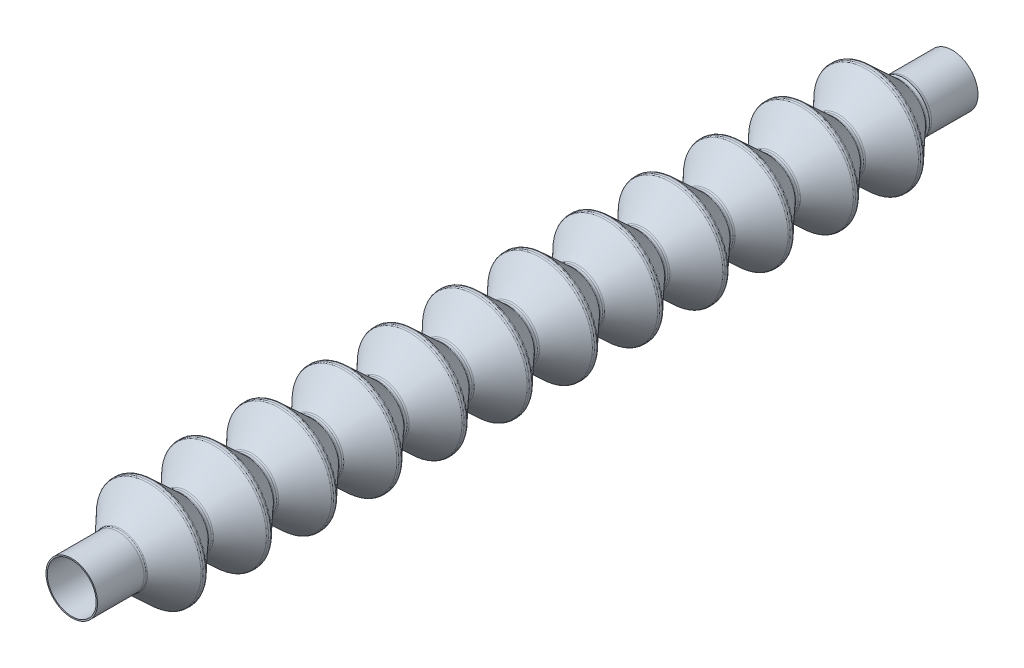
SolidWorks part; units mm, degrees
ref_plane "Front Plane" through (0, 0, 0) normal (0, 0, 1) x (1, 0, 0)
ref_plane "Top Plane" through (0, 0, 0) normal (0, 1, 0) x (1, 0, 0)
ref_plane "Right Plane" through (0, 0, 0) normal (1, 0, 0) x (0, 0, -1)
sketch "Sketch1" plane through (0, 0, 0) normal (1, 0, 0) x (0, 0, -1)
  line L0 (-152.4, 0) -> (152.4, 0) construction
  line L1 (0, -20.6375) -> (0, 20.6375) construction
  line L2 (-152.4, -9.525) -> (-152.4, 9.525) construction
  line L3 (-152.4, 0) -> (-171.45, 0) construction
  line L4 (152.4, 0) -> (171.45, 0) construction
  point P0 (-85.725, 0)
  point P3 (-152.4, 20.6375)
  point P4 (0, 0)
  point P8 (0, 0)
  point P11 (-152.4, 0)
  point P12 (0, 20.1295)
  point P13 (-152.4, 4.7625)
  point P14 (152.4, 20.6375)
  dimension "Retracted Length" = 66.675
  dimension "OD" = 41.275
  dimension "ID" = 19.05
  dimension "Required ID Clearance" = 4.7625
  dimension "Extended Length" = 304.8
  dimension "Cuff Length" = 19.05
sketch "Sketch2" plane through (0, 0, 0) normal (1, 0, 0) x (0, 0, -1)
  line L1 (-152.4, 9.525) -> (152.4, 9.525) construction
  line L7 (-152.4, 10.2195) -> (-141.224, 20.6375)
  line L9 (-152.4, 9.525) -> (-141.224, 19.943) construction
  line L108 (-153.8304, 10.8584) -> (-152.4, 9.525) construction
  line L109 (-152.4, 9.525) -> (-140.8776, 20.2659) construction
  line L163 (-152.4, 20.6375) -> (152.4, 20.6375) construction
  line L164 (-141.224, 20.6375) -> (-139.7, 20.6375)
  line L165 (-139.7, 20.6375) -> (-128.524, 10.2195)
  line L166 (-141.224, 19.943) -> (-139.7, 19.943) construction
  line L167 (-139.7, 19.943) -> (-128.524, 9.525) construction
  line L168 (-152.4, 9.525) -> (-141.224, 19.943)
  line L169 (-128.524, 10.2195) -> (-127, 10.2195)
  line L170 (-127, 10.2195) -> (-115.824, 20.6375)
  line L171 (-141.224, 19.943) -> (-139.7, 19.943)
  line L172 (-115.824, 20.6375) -> (-114.3, 20.6375)
  line L173 (-114.3, 20.6375) -> (-103.124, 10.2195)
  line L174 (-103.124, 10.2195) -> (-101.6, 10.2195)
  line L175 (-153.484, 11.23) -> (-152.4, 10.2195) construction
  line L176 (-101.6, 10.2195) -> (-90.424, 20.6375)
  line L177 (-90.424, 20.6375) -> (-88.9, 20.6375)
  line L178 (-88.9, 20.6375) -> (-77.724, 10.2195)
  line L179 (-77.724, 10.2195) -> (-76.2, 10.2195)
  line L180 (-76.2, 10.2195) -> (-65.024, 20.6375)
  line L181 (-65.024, 20.6375) -> (-63.5, 20.6375)
  line L182 (-63.5, 20.6375) -> (-52.324, 10.2195)
  line L183 (-52.324, 10.2195) -> (-50.8, 10.2195)
  line L184 (-50.8, 10.2195) -> (-39.624, 20.6375)
  line L185 (-39.624, 20.6375) -> (-38.1, 20.6375)
  line L186 (-38.1, 20.6375) -> (-26.924, 10.2195)
  line L187 (-26.924, 10.2195) -> (-25.4, 10.2195)
  line L188 (-25.4, 10.2195) -> (-14.224, 20.6375)
  line L189 (-14.224, 20.6375) -> (-12.7, 20.6375)
  line L190 (-12.7, 20.6375) -> (-1.524, 10.2195)
  line L191 (-1.524, 10.2195) -> (0, 10.2195)
  line L192 (0, 10.2195) -> (11.176, 20.6375)
  line L193 (11.176, 20.6375) -> (12.7, 20.6375)
  line L194 (12.7, 20.6375) -> (23.876, 10.2195)
  line L195 (23.876, 10.2195) -> (25.4, 10.2195)
  line L196 (25.4, 10.2195) -> (36.576, 20.6375)
  line L197 (36.576, 20.6375) -> (38.1, 20.6375)
  line L198 (38.1, 20.6375) -> (49.276, 10.2195)
  line L199 (49.276, 10.2195) -> (50.8, 10.2195)
  line L200 (50.8, 10.2195) -> (61.976, 20.6375)
  line L201 (61.976, 20.6375) -> (63.5, 20.6375)
  line L202 (63.5, 20.6375) -> (74.676, 10.2195)
  line L203 (74.676, 10.2195) -> (76.2, 10.2195)
  line L204 (76.2, 10.2195) -> (87.376, 20.6375)
  line L205 (87.376, 20.6375) -> (88.9, 20.6375)
  line L206 (88.9, 20.6375) -> (100.076, 10.2195)
  line L207 (100.076, 10.2195) -> (101.6, 10.2195)
  line L208 (101.6, 10.2195) -> (112.776, 20.6375)
  line L209 (112.776, 20.6375) -> (114.3, 20.6375)
  line L210 (114.3, 20.6375) -> (125.476, 10.2195)
  line L211 (125.476, 10.2195) -> (127, 10.2195)
  line L212 (127, 10.2195) -> (138.176, 20.6375)
  line L213 (138.176, 20.6375) -> (139.7, 20.6375)
  line L214 (139.7, 20.6375) -> (150.876, 10.2195)
  line L215 (150.876, 10.2195) -> (152.4, 10.2195)
  line L231 (-139.7, 19.943) -> (-128.524, 9.525)
  line L232 (-128.524, 9.525) -> (-127, 9.525)
  line L235 (-127, 9.525) -> (-115.824, 19.943)
  line L236 (-115.824, 19.943) -> (-114.3, 19.943)
  line L237 (-114.3, 19.943) -> (-103.124, 9.525)
  line L238 (-103.124, 9.525) -> (-101.6, 9.525)
  line L239 (-101.6, 9.525) -> (-90.424, 19.943)
  line L240 (-90.424, 19.943) -> (-88.9, 19.943)
  line L241 (-88.9, 19.943) -> (-77.724, 9.525)
  line L242 (-77.724, 9.525) -> (-76.2, 9.525)
  line L243 (-76.2, 9.525) -> (-65.024, 19.943)
  line L244 (-65.024, 19.943) -> (-63.5, 19.943)
  line L245 (-63.5, 19.943) -> (-52.324, 9.525)
  line L246 (-52.324, 9.525) -> (-50.8, 9.525)
  line L247 (-50.8, 9.525) -> (-39.624, 19.943)
  line L248 (-39.624, 19.943) -> (-38.1, 19.943)
  line L249 (-38.1, 19.943) -> (-26.924, 9.525)
  line L250 (-26.924, 9.525) -> (-25.4, 9.525)
  line L251 (-25.4, 9.525) -> (-14.224, 19.943)
  line L252 (-14.224, 19.943) -> (-12.7, 19.943)
  line L253 (-12.7, 19.943) -> (-1.524, 9.525)
  line L254 (-1.524, 9.525) -> (0, 9.525)
  line L255 (0, 9.525) -> (11.176, 19.943)
  line L256 (11.176, 19.943) -> (12.7, 19.943)
  line L257 (12.7, 19.943) -> (23.876, 9.525)
  line L258 (23.876, 9.525) -> (25.4, 9.525)
  line L259 (25.4, 9.525) -> (36.576, 19.943)
  line L260 (36.576, 19.943) -> (38.1, 19.943)
  line L261 (38.1, 19.943) -> (49.276, 9.525)
  line L262 (49.276, 9.525) -> (50.8, 9.525)
  line L263 (50.8, 9.525) -> (61.976, 19.943)
  line L264 (61.976, 19.943) -> (63.5, 19.943)
  line L265 (63.5, 19.943) -> (74.676, 9.525)
  line L266 (74.676, 9.525) -> (76.2, 9.525)
  line L267 (76.2, 9.525) -> (87.376, 19.943)
  line L268 (87.376, 19.943) -> (88.9, 19.943)
  line L269 (88.9, 19.943) -> (100.076, 9.525)
  line L270 (100.076, 9.525) -> (101.6, 9.525)
  line L271 (101.6, 9.525) -> (112.776, 19.943)
  line L272 (112.776, 19.943) -> (114.3, 19.943)
  line L273 (114.3, 19.943) -> (125.476, 9.525)
  line L274 (125.476, 9.525) -> (127, 9.525)
  line L275 (127, 9.525) -> (138.176, 19.943)
  line L276 (138.176, 19.943) -> (139.7, 19.943)
  line L277 (139.7, 19.943) -> (150.876, 9.525)
  line L278 (150.876, 9.525) -> (152.4, 9.525)
  line L294 (-152.4, 9.525) -> (-152.4, 10.2195)
  line L295 (152.4, 9.525) -> (152.4, 10.2195)
  line L297 (152.4, 10.2195) -> (163.576, 20.6375) [skipped]
  point P10 (-127.762, 10.2195)
  dimension "D2" = 0.508
  dimension "D1" = 1.524
  dimension "D5" = 25.4
  dimension "D4" = 12.7
  dimension "D3" = 12
  dimension "D6" = 2
revolve "Revolve3" add sketch "Sketch2" angle 360 about L0
sketch "Sketch5" plane through (0, 0, 0) normal (1, 0, 0) x (0, 0, -1)
  line L2 (-152.4, 9.525) -> (-152.4, 10.033)
  line L7 (-152.4, 10.033) -> (-171.45, 10.033)
  line L29 (-171.45, 10.033) -> (-171.45, 9.525)
  line L30 (-171.45, 9.525) -> (-152.4, 9.525)
  line L31 (152.4, 9.525) -> (171.45, 9.525)
  line L32 (171.45, 9.525) -> (171.45, 10.033)
  line L33 (171.45, 10.033) -> (152.4, 10.033)
  line L34 (152.4, 10.033) -> (152.4, 9.525)
  dimension "D1" = 0.508
revolve "Revolve2" add sketch "Sketch5" angle 360 about L3
fillet "Fillet3" radius 2.54 2 edges at (0, 10.033, -152.4) (0, 10.033, 152.4)
fillet "Fillet1" radius 0.889 24 edges at (0, -10.2195, -150.876) (0, -20.6375, -139.7) (0, -10.2195, -125.476) (0, -20.6375, -114.3) (0, -10.2195, -100.076) (0, -20.6375, -88.9) (0, -10.2195, -74.676) (0, -20.6375, -63.5) (0, -10.2195, -49.276) (0, -20.6375, -38.1) (0, -10.2195, -23.876) (0, -20.6375, -12.7) (0, -10.2195, 1.524) (0, -20.6375, 12.7) (0, -10.2195, 26.924) (0, -20.6375, 38.1) (0, -10.2195, 52.324) (0, -20.6375, 63.5) (0, -10.2195, 77.724) (0, -20.6375, 88.9) (0, -10.2195, 103.124) (0, -20.6375, 114.3) (0, -10.2195, 128.524) (0, -20.6375, 139.7)
fillet "Fillet2" radius 0.889 24 edges at (0, -10.2195, 152.4) (0, -20.6375, -138.176) (0, -10.2195, -127) (0, -20.6375, -112.776) (0, -10.2195, -101.6) (0, -20.6375, -87.376) (0, -10.2195, -76.2) (0, -20.6375, -61.976) (0, -10.2195, -50.8) (0, -20.6375, -36.576) (0, -10.2195, -25.4) (0, -20.6375, -11.176) (0, -10.2195, 0) (0, -20.6375, 14.224) (0, -10.2195, 25.4) (0, -20.6375, 39.624) (0, -10.2195, 50.8) (0, -20.6375, 65.024) (0, -10.2195, 76.2) (0, -20.6375, 90.424) (0, -10.2195, 101.6) (0, -20.6375, 115.824) (0, -10.2195, 127) (0, -20.6375, 141.224)
sketch "Sketch3" plane through (0, 0, 0) normal (1, 0, 0) x (0, 0, -1)
  line L0 (-171.45, 0) -> (171.45, 0) construction
  point P7 (-64.262, 0)
  point P8 (62.738, 0)
  dimension "D1" = 64.262
  dimension "D2" = 62.738
sketch "Sketch6" plane through (0, 0, 0) normal (0, 0, 1) x (1, 0, 0)
  line L0 (-9.525, 0) -> (9.525, 0)
  line L2 (-20.6375, 0) -> (20.6375, 0)
  point P4 (0, 0)
  point P8 (0, 0)
  point P9 (-9.525, 0)
  point P10 (20.6375, 0)
  point P11 (-20.6375, 0)
  dimension "D1" = 41.275
  dimension "D2" = 19.05
equation "\"D2@Sketch2\"=\"Thickness@Sketch1\""
equation "\"D1@Sketch3\"=( \"D4@Sketch2\" * 5 )  + \"Thickness@Sketch1\"*1.5"
equation "\"D2@Sketch3\"=\"D1@Sketch3\" - (\"Thickness@Sketch1\"*3)"
equation "\"D1@Sketch2\"=\"Thickness@Sketch1\"*3"
equation "\"D1@Sketch5\"=\"thickness@sketch1\""
equation "\"D1@Sketch6\"=\"od@sketch1\""
equation "\"D2@Sketch6\"=\"id@sketch1\""
